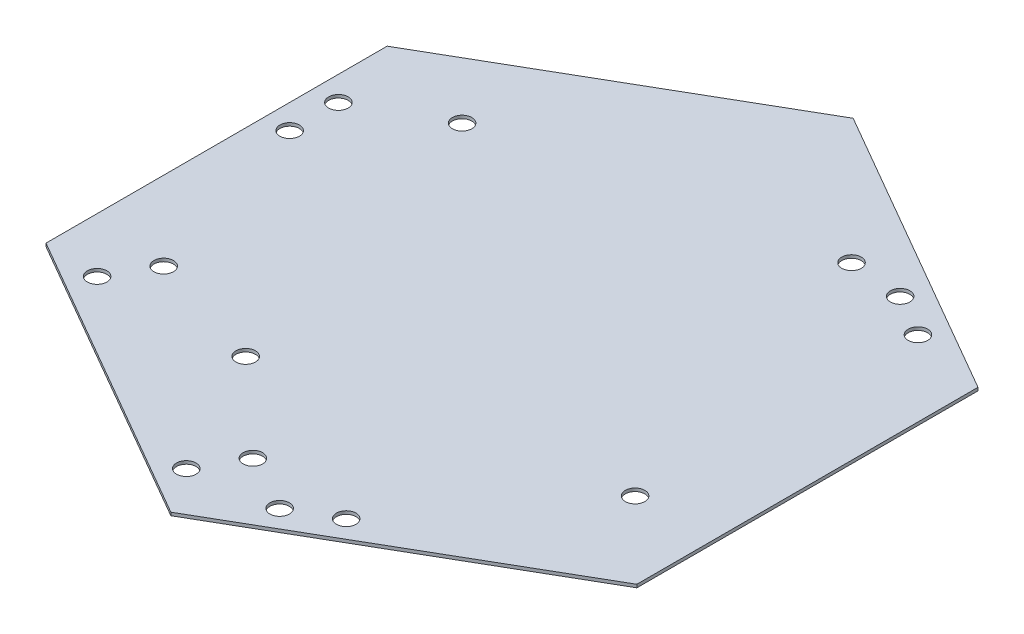
SolidWorks part; units mm, degrees
material "5052-H32"
ref_plane "Front Plane" through (0, 0, 0) normal (0, 0, 1) x (1, 0, 0)
ref_plane "Top Plane" through (0, 0, 0) normal (0, 1, 0) x (1, 0, 0)
ref_plane "Right Plane" through (0, 0, 0) normal (1, 0, 0) x (0, 0, -1)
sketch "Sketch1" plane through (0, 0, 0) normal (0, 1, 0) x (1, 0, 0)
  line L0 (13.3228, -73.8757) -> (24.3213, -67.5257) construction
  line L1 (0, 88.9) -> (-76.9897, 44.45)
  line L2 (-76.9897, 44.45) -> (-76.9897, -44.45)
  line L3 (-76.9897, -44.45) -> (0, -88.9)
  line L4 (0, -88.9) -> (76.9897, -44.45)
  line L5 (76.9897, -44.45) -> (76.9897, 44.45)
  line L6 (76.9897, 44.45) -> (0, 88.9)
  line L7 (24.3213, -67.5257) -> (27.4963, -73.025) construction
  line L8 (-70.6397, 12.7) -> (-76.9897, 12.7) construction
  line L9 (-70.6397, 25.4) -> (-70.6397, 12.7) construction
  line L10 (46.3184, 54.8257) -> (49.4934, 60.325) construction
  line L11 (57.3169, 48.4757) -> (46.3184, 54.8257) construction
  circle A0 centre (0, 0) radius 76.9897 construction
  circle A1 centre (13.3228, -73.8757) radius 2.54
  circle A2 centre (24.3213, -67.5257) radius 2.54
  circle A7 centre (-70.6397, 12.7) radius 2.54
  circle A8 centre (-70.6397, 25.4) radius 2.54
  circle A9 centre (46.3184, 54.8257) radius 2.54
  circle A10 centre (57.3169, 48.4757) radius 2.54
  point P13 (38.4948, -66.675)
  point P28 (3.175, -1.8331)
  point P29 (0, 0)
  dimension "D2" = 5.08
  dimension "D3" = 6.35
  dimension "D4" = 12.7
  dimension "D1" = 177.8
  dimension "D5" = 12.7
  dimension "D6" = 3
extrude "Boss-Extrude1" add sketch "Sketch1" along normal blind 0.8128
sketch "Sketch2" plane through (0, 0.8128, 0) normal (0, 1, 0) x (1, 0, 0)
  line L1 (27.9428, -74.7916) -> (-78.7428, -13.1966) construction
  line L2 (27.9428, -74.7916) -> (85.7278, 25.295) construction
  line L3 (85.7278, 25.295) -> (-20.9578, 86.89) construction
  line L4 (-78.7428, -13.1966) -> (-20.9578, 86.89) construction
  line L5 (-76.9897, -44.45) -> (0, -88.9) construction
  circle A0 centre (-49.8503, 36.8467) radius 2.54
  circle A1 centre (-25.4, -43.9941) radius 2.54
  circle A2 centre (32.385, 56.0925) radius 2.54
  circle A3 centre (56.8353, -24.7483) radius 2.54
  point P4 (-227.1222, 125.1667)
  point P5 (-102.9802, 121.9637)
  point P6 (-152.0605, 136.3655)
  dimension "D5" = 5.08
  dimension "D1" = 123.19
  dimension "D2" = 115.57
  dimension "D3" = 61.595
  dimension "D4" = 50.8
extrude "Cut-Extrude1" cut sketch "Sketch2" against normal through all
sketch "Sketch3" plane through (0, 0.8128, 0) normal (0, 1, 0) x (1, 0, 0)
  line L0 (-62.8161, -45.3007) -> (-65.9911, -50.8) construction
  line L2 (-76.9897, -44.45) -> (0, -88.9) construction
  line L3 (-62.8161, -45.3007) -> (-7.8235, -77.0507) construction
  line L4 (-35.3198, -61.1757) -> (-38.4948, -66.675) construction
  line L5 (-56.4661, -34.3022) -> (-62.8161, -45.3007) construction
  line L6 (-56.4661, -34.3022) -> (-1.4735, -66.0522) construction
  circle A1 centre (-7.8235, -77.0507) radius 2.54
  circle A2 centre (-62.8161, -45.3007) radius 2.54
  circle A3 centre (-56.4661, -34.3022) radius 2.54
  circle A4 centre (-1.4735, -66.0522) radius 2.54
  dimension "D1" = 5.08
  dimension "D2" = 6.35
  dimension "D3" = 63.5
  dimension "D4" = 12.7
extrude "Cut-Extrude2" cut sketch "Sketch3" against normal through all
